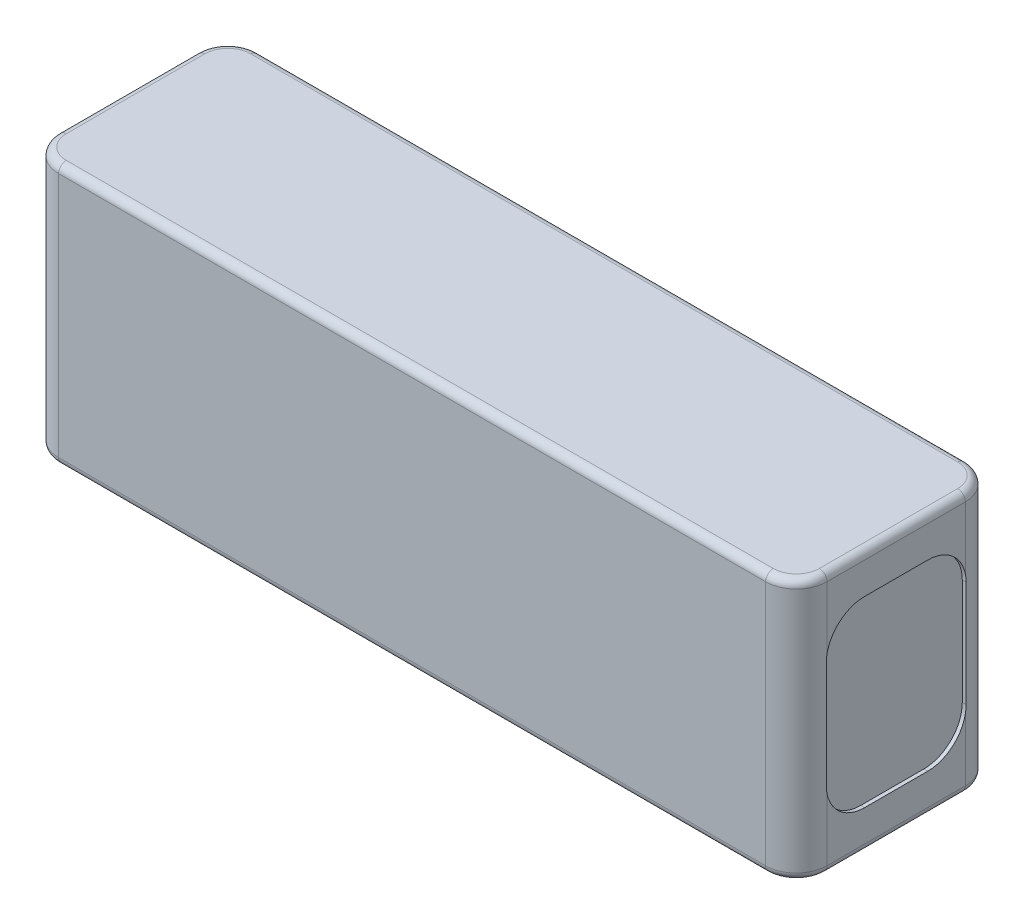
SolidWorks part; units mm, degrees
ref_plane "Front Plane" through (0, 0, 0) normal (0, 0, 1) x (1, 0, 0)
ref_plane "Top Plane" through (0, 0, 0) normal (0, 1, 0) x (1, 0, 0)
ref_plane "Right Plane" through (0, 0, 0) normal (1, 0, 0) x (0, 0, -1)
ref_plane "Plane1" through (0, 0, -15) normal (0, 0, -1) x (-1, 0, 0)
sketch "Sketch1" plane through (0, 0, -15) normal (0, 0, -1) x (-1, 0, 0)
  line L0 (-69, -22) -> (31, -22)
  line L1 (31, -22) -> (31, 12)
  line L2 (31, 12) -> (-69, 12)
  line L3 (-69, 12) -> (-69, -22)
  line L4 (-69, -5) -> (31, -5) construction
  line L5 (-19, 12) -> (-19, -22) construction
  dimension "D1" = 34
  dimension "D2" = 100
extrude "Boss-Extrude1" add sketch "Sketch1" against normal blind 26
sketch "Sketch2" plane through (69, 0, 0) normal (1, 0, 0) x (0, 0, -1)
  line L0 (-7.1, 1.9) -> (-7.1, -11.9)
  line L1 (-2.1, -16.9) -> (6.1, -16.9)
  line L2 (11.1, -11.9) -> (11.1, 1.9)
  line L3 (6.1, 6.9) -> (-2.1, 6.9)
  line L4 (-11, 12) -> (15, -22) construction
  line L5 (15, 12) -> (-11, -22) construction
  line L6 (-7.1, 6.9) -> (11.1, -16.9) construction
  line L7 (11.1, 6.9) -> (-7.1, -16.9) construction
  line L12 (-11, 12) -> (15, 12) construction
  line L13 (-11, 12) -> (-11, -22) construction
  line L14 (-11, -22) -> (15, -22) construction
  line L15 (15, 12) -> (15, -22) construction
  line L16 (-11, 12) -> (15, -22) construction
  line L17 (-11, -22) -> (15, 12) construction
  arc A0 (-7.1, -11.9) -> (-2.1, -16.9) centre (-2.1, -11.9) ccw
  arc A1 (6.1, -16.9) -> (11.1, -11.9) centre (6.1, -11.9) ccw
  arc A2 (11.1, 1.9) -> (6.1, 6.9) centre (6.1, 1.9) ccw
  arc A3 (-7.1, 1.9) -> (-2.1, 6.9) centre (-2.1, 1.9) cw
  point P16 (2, -5)
  dimension "D2" = 26
  dimension "D3" = 5
  dimension "D1" = 18.2
extrude "Cut-Extrude1" cut sketch "Sketch2" against normal blind 0.5
sketch "Sketch3" plane through (-31, 0, 0) normal (-1, 0, 0) x (0, 0, 1)
  line L0 (-0.25, 7.75) -> (-3.75, 7.75)
  line L1 (-11.75, -0.25) -> (-11.75, -9.75)
  line L2 (-3.75, -17.75) -> (-0.25, -17.75)
  line L3 (7.75, -9.75) -> (7.75, -0.25)
  line L4 (-11.75, 7.75) -> (7.75, -17.75) construction
  line L5 (7.75, 7.75) -> (-11.75, -17.75) construction
  line L6 (-15, 12) -> (11, -22) construction
  line L7 (11, -22) -> (-15, -22) construction
  line L8 (-15, -22) -> (11, 12) construction
  arc A0 (-11.75, -9.75) -> (-3.75, -17.75) centre (-3.75, -9.75) ccw
  arc A1 (-0.25, -17.75) -> (7.75, -9.75) centre (-0.25, -9.75) ccw
  arc A2 (-0.25, 7.75) -> (7.75, -0.25) centre (-0.25, -0.25) cw
  arc A3 (-3.75, 7.75) -> (-11.75, -0.25) centre (-3.75, -0.25) ccw
  dimension "D3" = 8
  dimension "D1" = 19.5
  dimension "D2" = 26
extrude "Cut-Extrude2" cut sketch "Sketch3" against normal blind 0.5
fillet "Fillet1" radius 4 4 edges at (-31, -5, -15) (-31, -5, 11) (69, -5, -15) (69, -5, 11) tangent propagation no
fillet "Fillet2" radius 1 16 edges at (67.8284, 12, -13.8284) (69, 12, -2) (19, 12, -15) (67.8284, 12, 9.8284) (-29.8284, 12, -13.8284) (19, 12, 11) (-31, 12, -2) (-29.8284, 12, 9.8284) (-31, -22, -2) (-29.8284, -22, -13.8284) (-29.8284, -22, 9.8284) (19, -22, -15) (19, -22, 11) (67.8284, -22, -13.8284) (67.8284, -22, 9.8284) (69, -22, -2) tangent propagation no
sketch "Sketch4" [suppressed] plane through (0, 0, 10) normal (0, 0, 1) x (1, 0, 0)
  line L0 (-75, 4) -> (65, 4) construction
  line L1 (-75, 29) -> (-75, -21) construction
  line L2 (65, -21) -> (65, 29) construction
  line L3 (-5, 25.9735) -> (-5, -21) construction
  line L4 (-75, -21) -> (65, -21) construction
  circle A0 centre (-5, 4) radius 0.5026
sketch "Sketch5" plane through (68.5, 0, 0) normal (1, 0, 0) x (0, 0, -1)
  line L0 (7, 8) -> (-3, 8) construction
  line L1 (2, 12) -> (2, 8) construction
  line L2 (-7, 12) -> (11, 12) construction
  circle A0 centre (-3, 8) radius 2
  circle A1 centre (7, 8) radius 2
  dimension "D1" = 4
  dimension "D2" = 10
  dimension "D3" = 4
equation "\"D1@Sketch3\"=\"D2@Sketch3\" * .75"
equation "\"D1@Sketch2\"=\"D2@Sketch2\"* .7"
